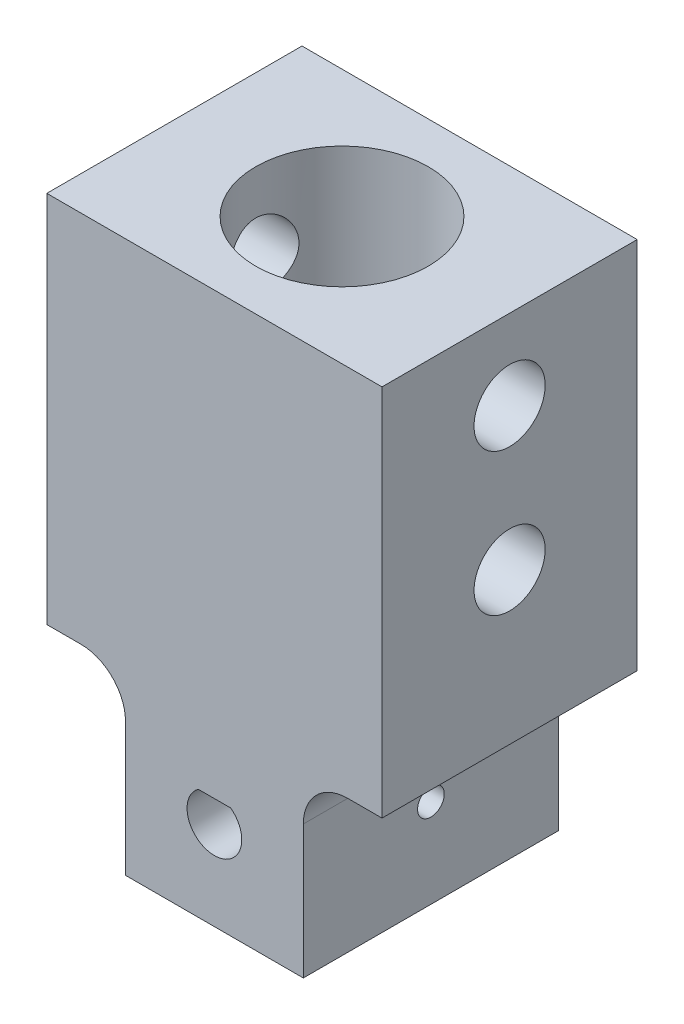
SolidWorks part; units mm, degrees
material "Plain Carbon Steel"
ref_plane "Front" through (0, 0, 0) normal (0, 0, 1) x (1, 0, 0)
ref_plane "Top" through (0, 0, 0) normal (0, 1, 0) x (1, 0, 0)
ref_plane "Right" through (0, 0, 0) normal (1, 0, 0) x (0, 0, -1)
sketch "Sketch11" plane through (0, 0, 0) normal (0, 1, 0) x (1, 0, 0)
  line L1 (-18.85, 14.35) -> (18.85, 14.35)
  line L2 (-18.85, 14.35) -> (-18.85, -14.35)
  line L3 (-18.85, -14.35) -> (18.85, -14.35)
  line L4 (18.85, 14.35) -> (18.85, -14.35)
  line L5 (-18.85, 14.35) -> (18.85, -14.35) construction
  line L6 (-18.85, -14.35) -> (18.85, 14.35) construction
  circle A0 centre (0, 0) radius 9.7
  point P0 (0, 0)
  dimension "D3" = 19.4
  dimension "D1" = 37.7
  dimension "D2" = 28.7
extrude "Boss-Extrude1" add sketch "Sketch11" along normal blind 42
sketch "Sketch15" plane through (0, 0, 14.35) normal (0, 0, 1) x (1, 0, 0)
  line L0 (18.85, 42) -> (18.85, 0) construction
  line L1 (-18.85, 0) -> (18.85, 0)
  line L2 (-18.85, 0) -> (-18.85, 5)
  line L3 (-18.85, 5) -> (18.85, 5)
  line L4 (18.85, 0) -> (18.85, 5)
  dimension "D1" = 5
extrude "Boss-Extrude3" add sketch "Sketch15" against normal up to surface (28.7 mm away) up to face at (0, 21, -14.35)
sketch "Sketch12" plane through (18.85, 0, 0) normal (1, 0, 0) x (0, 0, -1)
  line L0 (-22.564, 25) -> (28.4467, 25) construction
  circle A0 centre (0, 33) radius 4
  circle A1 centre (0, 17) radius 4
  dimension "D1" = 25
  dimension "D2" = 8
  dimension "D3" = 8
extrude "Cut-Extrude1" cut sketch "Sketch12" against normal blind 40
sketch "Sketch23" plane through (0, 0, 0) normal (0, 0, 1) x (1, 0, 0)
  line L0 (0, -10) -> (0, -13.075) construction
  line L1 (-10, 0) -> (10, 0)
  line L2 (-10, 0) -> (-10, -20)
  line L3 (-10, -20) -> (10, -20)
  line L4 (10, 0) -> (10, -20)
  line L5 (-10, 0) -> (10, -20) construction
  line L6 (-10, -20) -> (10, 0) construction
  line L7 (-1.8248, -7.525) -> (1.8248, -7.525)
  circle A0 centre (0, -10) radius 3.075
  point P0 (0, -10)
  dimension "D3" = 6.15
  dimension "D1" = 10
  dimension "D4" = 5.55
extrude "Boss-Extrude4" add sketch "Sketch23" against normal mid plane 28.7 contours L4 L1 L2 L3 A0 | L7 A0 region at (0, -0.2828, 0) region at (0, -7.2829, 0)
sketch "Sketch24" plane through (0, 0, 0) normal (1, 0, 0) x (0, 0, -1)
  circle A0 centre (0, -10) radius 1.5
  dimension "D1" = 3
  dimension "D2" = 10
extrude "Cut-Extrude2" cut sketch "Sketch24" against normal through all both and the other way through all
fillet "Fillet1" radius 5 2 edges at (-10, 0, 0) (10, 0, 0)
